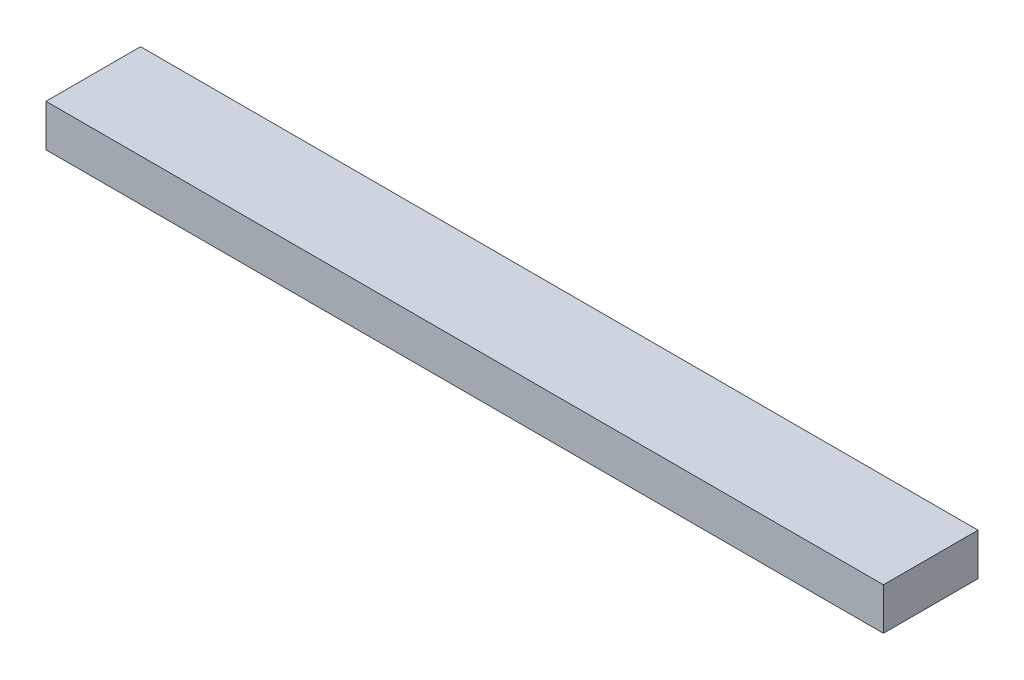
SolidWorks part; units mm, degrees
material "MDF"
ref_plane "Front Plane" through (0, 0, 0) normal (0, 0, 1) x (1, 0, 0)
ref_plane "Top Plane" through (0, 0, 0) normal (0, 1, 0) x (1, 0, 0)
ref_plane "Right Plane" through (0, 0, 0) normal (1, 0, 0) x (0, 0, -1)
sketch "Sketch1" plane through (0, 0, 0) normal (0, 0, 1) x (1, 0, 0)
  line L0 (0, -297.4265) -> (0, 297.4265) construction
  line L1 (-126.4888, -311.15) -> (126.4888, -311.15)
  line L2 (-126.4888, -311.15) -> (-126.4888, -298.45)
  line L3 (-126.4888, -298.45) -> (126.4888, -298.45)
  line L4 (0, -311.15) -> (0, -298.45) construction
  line L5 (126.4888, -311.15) -> (126.4888, -298.45)
  dimension "D1" = 12.7
extrude "Boss-Extrude1" add sketch "Sketch1" along normal up to surface (28.575 mm away)
hole_wizard "Hole1" positions "Sketch2" profile "Sketch3" legacy
sketch "Sketch2" plane through (0, 0, -25.4) normal (0, 0, -1) x (-1, 0, 0)
  line L0 (218.5638, 0) -> (218.5638, -437.642) construction
  line L4 (104.2638, 0) -> (104.2638, -298.45) construction
  line L13 (120.1388, -463.55) -> (120.1388, -311.15) construction
  line L16 (126.4888, -311.15) -> (113.7888, -311.15) construction
  line L18 (126.4888, -304.8) -> (-126.4888, -304.8) construction
  line L22 (94.7388, -276.225) -> (-94.7388, -276.225) construction
  line L24 (-94.7388, -285.75) -> (-94.7388, -266.7) construction
  line L26 (94.7388, -285.75) -> (94.7388, -266.7) construction
  line L27 (-94.7388, 0) -> (-94.7388, -19.05) construction
  line L29 (94.7388, 0) -> (94.7388, -19.05) construction
  line L31 (94.7388, -9.525) -> (-94.7388, -9.525) construction
  point P15 (218.5638, -31.75)
  point P17 (218.5638, -218.821)
  point P19 (218.5638, -418.592)
  point P28 (104.2638, -19.05)
  point P30 (104.2638, -149.225)
  point P32 (104.2638, -279.4)
  point P69 (120.1388, -330.2)
  point P71 (120.1388, -444.5)
  point P76 (-120.1388, -444.5)
  point P77 (-120.1388, -330.2)
  point P80 (-104.2638, -279.4)
  point P81 (-104.2638, -149.225)
  point P82 (-104.2638, -19.05)
  point P83 (-218.5638, -418.592)
  point P84 (-218.5638, -218.821)
  point P85 (-218.5638, -31.75)
  point P99 (0, -304.8)
  point P101 (107.4388, -304.8)
  point P103 (-107.4388, -304.8)
  point P127 (75.6888, -276.225)
  point P129 (0, -276.225)
  point P131 (-75.6888, -276.225)
  point P152 (75.6888, -9.525)
  point P154 (0, -9.525)
  point P156 (-75.6888, -9.525)
sketch "Sketch3" plane through (75.6888, -9.525, -25.4) normal (1, 0, 0) x (0, 1, 0)
  line L0 (0, 0) -> (0, 39.0539)
  line L1 (0, 39.0539) -> (1.5875, 38.1)
  line L2 (1.5875, 38.1) -> (1.5875, 4.0177)
  line L3 (1.5875, 4.0177) -> (5.08, 0)
  line L4 (5.08, 0) -> (0, 0)
  line L5 (0, -14.3089) -> (0, 102.4216) construction
  line L6 (0, 39.0539) -> (-1.5875, 38.1) construction
  line L7 (-1.5875, 4.0177) -> (-5.08, 0) construction
  dimension "Diameter" = 3.175
  dimension "Depth" = 38.1
  dimension "C-Sink Diameter" = 10.16
  dimension "C-Sink Angle" = 82
  dimension "Drill Angle" = 118
